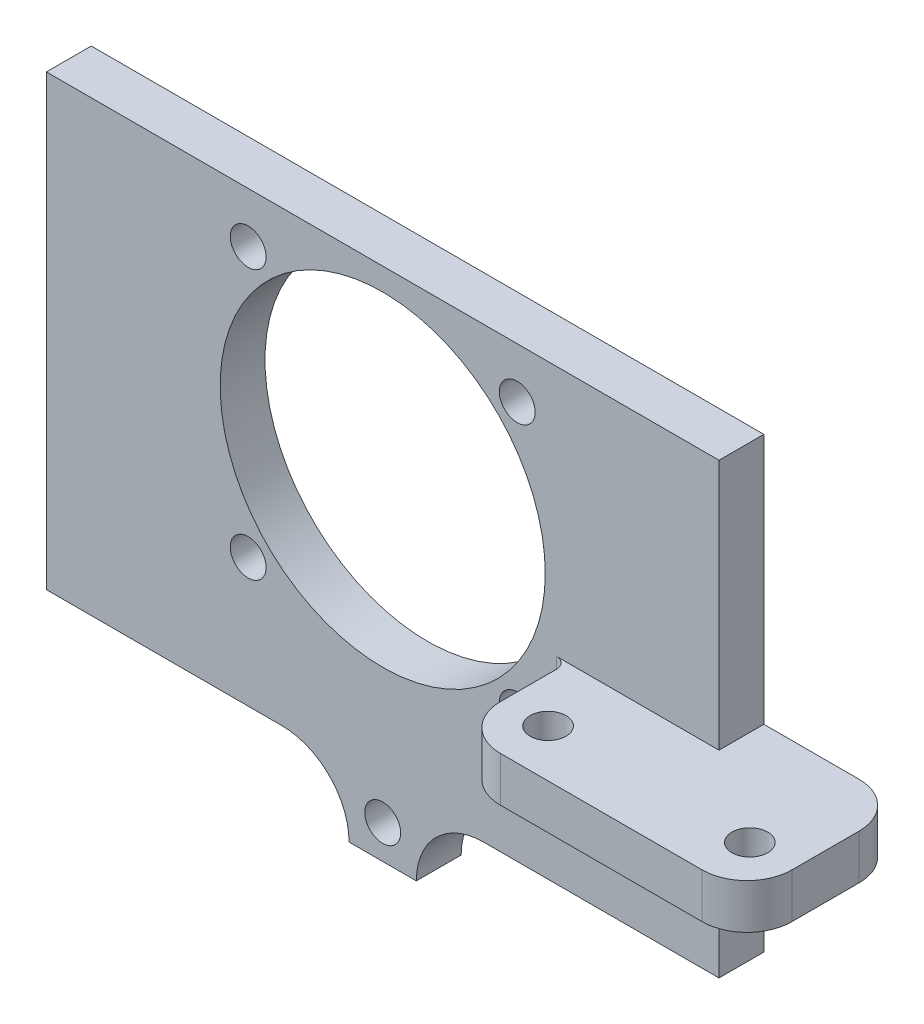
SolidWorks part; units mm, degrees
ref_plane "Płaszczyzna przednia" through (0, 0, 0) normal (0, 0, 1) x (1, 0, 0)
ref_plane "Płaszczyzna górna" through (0, 0, 0) normal (0, 1, 0) x (1, 0, 0)
ref_plane "Płaszczyzna prawa" through (0, 0, 0) normal (1, 0, 0) x (0, 0, -1)
sketch "Sketch1" plane through (0, 0, 0) normal (0, 0, 1) x (1, 0, 0)
  line L1 (0, 0) -> (60, 0)
  line L2 (0, 0) -> (0, 40)
  line L3 (0, 40) -> (60, 40)
  line L4 (60, 0) -> (60, 40)
  line L5 (0, 0) -> (60, 40) construction
  line L6 (0, 40) -> (60, 0) construction
  point P4 (30, 20)
  dimension "D1" = 60
  dimension "D2" = 40
extrude "Boss-Extrude1" add sketch "Sketch1" along normal blind 4
sketch "Sketch4" plane through (0, 0, 4) normal (0, 0, 1) x (1, 0, 0)
  line L0 (0, 40) -> (60, 0) construction
  line L1 (0, 0) -> (60, 40) construction
  line L2 (30, -0.7473) -> (30, 40.7473) construction
  line L3 (60, 40) -> (0, 40) construction
  circle A0 centre (30, 23.5) radius 14.5
  point P10 (30, 20)
  point P16 (30, 20)
  dimension "D1" = 29
  dimension "D2" = 16.5
extrude "Cut-Extrude1" cut sketch "Sketch4" against normal blind 4
sketch "Sketch6" plane through (0, 0, 4) normal (0, 0, 1) x (1, 0, 0)
  circle A0 centre (42, 11.5) radius 1.6
  circle A1 centre (18, 11.5) radius 1.6
  circle A2 centre (18, 35.5) radius 1.6
  circle A3 centre (42, 35.5) radius 1.6
  dimension "D1" = 3.2
  dimension "D2" = 3.2
  dimension "D3" = 3.2
  dimension "D4" = 3.2
extrude "Cut-Extrude2" cut sketch "Sketch6" against normal blind 4
sketch "Sketch7" plane through (0, 0, 4) normal (0, 0, 1) x (1, 0, 0)
  line L0 (56.5, 17.6) -> (62.5, 17.6) construction
  line L1 (46.5, 17.6) -> (72.5, 17.6)
  line L2 (46.5, 17.6) -> (46.5, 13.6)
  line L3 (46.5, 13.6) -> (72.5, 13.6)
  line L4 (72.5, 17.6) -> (72.5, 13.6)
  line L5 (46.5, 17.6) -> (72.5, 13.6) construction
  line L6 (46.5, 13.6) -> (72.5, 17.6) construction
  line L10 (59.5, 13.6) -> (59.5, 17.6) construction
  line L11 (62.5, 17.6) -> (62.5, 20) construction
  point P4 (59.5, 15.6)
  dimension "D1" = 4
  dimension "D2" = 26
  dimension "D3" = 3
extrude "Boss-Extrude3" add sketch "Sketch7" along normal blind 10
sketch "Sketch8" plane through (0, 17.6, 0) normal (0, 1, 0) x (1, 0, 0)
  circle A0 centre (68.5, -9.75) radius 1.6
  circle A1 centre (50.5, -9.75) radius 1.6
extrude "Cut-Extrude3" cut sketch "Sketch8" against normal through all
sketch "Sketch9" plane through (60, 0, 0) normal (1, 0, 0) x (0, 0, -1)
  line L0 (0, 0) -> (0, 40) construction
  line L1 (-4, 13.6) -> (0, 13.6)
  line L2 (-4, 13.6) -> (-4, 17.6)
  line L3 (-4, 17.6) -> (0, 17.6)
  line L4 (0, 13.6) -> (0, 17.6)
  line L5 (-4, 13.6) -> (0, 17.6) construction
  line L6 (-4, 17.6) -> (0, 13.6) construction
  point P4 (-2, 15.6)
  point P8 (-4, 17.6)
extrude "Boss-Extrude4" add sketch "Sketch9" along normal blind 12.5
fillet "Fillet2" radius 4 3 edges at (72.5, 15.6, 14) (46.5, 15.6, 14) (72.5, 15.6, 0)
fillet "Fillet3" radius 1 3 edges at (60, 13.6, 2) (53.25, 13.6, 4) (46.5, 15.6, 4)
sketch "Sketch10" plane through (0, 0, 0) normal (0, -1, 0) x (1, 0, 0)
  line L0 (0, 4) -> (60, 4) construction
  line L1 (33, 4) -> (27, 4)
  line L2 (33, 4) -> (33, 0)
  line L3 (33, 0) -> (27, 0)
  line L4 (27, 4) -> (27, 0)
  line L5 (33, 4) -> (27, 0) construction
  line L6 (33, 0) -> (27, 4) construction
  line L7 (0, 0) -> (60, 0) construction
  line L8 (60, 4) -> (60, 0) construction
  line L9 (0, 4) -> (0, 0) construction
  point P4 (30, 2)
  point P9 (33, 2)
  dimension "D1" = 6
  dimension "D2" = 27
  dimension "D3" = 27
extrude "Boss-Extrude5" add sketch "Sketch10" along normal blind 6
fillet "Fillet4" radius 6 2 edges at (27, 0, 2) (33, 0, 2)
hole_wizard "Ø3.2 (3.2) Diameter Hole1" positions "Sketch11" profile "Sketch12" hole size "Ø3.2" standard "ANSI Metric" end condition up to next
sketch "Sketch11" plane through (0, 0, 4) normal (0, 0, 1) x (1, 0, 0)
  line L0 (33, -6) -> (27, -6) construction
  point P0 (30, -3)
  dimension "D1" = 3
  dimension "D2" = 3
sketch "Sketch12" plane through (30, -3, 4) normal (1, 0, 0) x (0, -1, 0)
  line L0 (0, 0) -> (0, 4)
  line L1 (0, 4) -> (1.6, 4)
  line L2 (1.6, 4) -> (1.6, 0)
  line L5 (1.6, 0) -> (0, 0)
  line L11 (0, -6.35) -> (0, 107.95) construction
  dimension "Thru Hole Dia." = 3.2
  dimension "Thru Hole Depth" = 4
